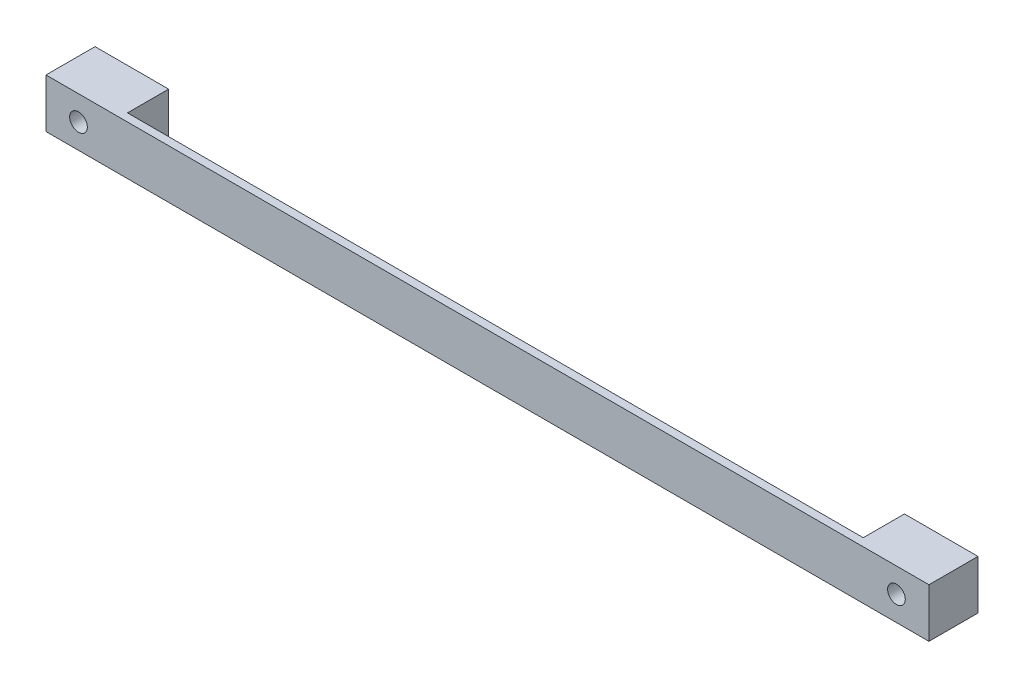
SolidWorks part; units mm, degrees
ref_plane "Front Plane" through (0, 0, 0) normal (0, 0, 1) x (1, 0, 0)
ref_plane "Top Plane" through (0, 0, 0) normal (0, 1, 0) x (1, 0, 0)
ref_plane "Right Plane" through (0, 0, 0) normal (1, 0, 0) x (0, 0, -1)
sketch "Sketch1" plane through (0, 0, 0) normal (0, 0, 1) x (1, 0, 0)
  line L1 (0, 0) -> (228.6, 0)
  line L2 (0, 0) -> (0, 12.7)
  line L3 (0, 12.7) -> (228.6, 12.7)
  line L4 (228.6, 0) -> (228.6, 12.7)
  dimension "D1" = 12.7
  dimension "D2" = 228.6
extrude "Boss-Extrude1" add sketch "Sketch1" along normal blind 12.7
ref_plane "Plane2" through (114.3, 0, 0) normal (1, 0, 0) x (0, 0, -1)
sketch "Sketch2" plane through (114.3, 0, 0) normal (1, 0, 0) x (0, 0, -1)
  line L0 (-10.6566, 12.7) -> (0, 0)
  line L1 (-12.7, 12.7) -> (0, 12.7) construction
  line L2 (0, 0) -> (0, 12.7) construction
  line L3 (0, 0) -> (0, 12.7)
  line L4 (0, 12.7) -> (-10.6566, 12.7)
  point P6 (0, 2.3854)
  point P8 (0, 0)
  point P10 (0, 0)
  dimension "D1" = 50
extrude "Cut-Extrude1" cut sketch "Sketch2" against normal mid plane 190.5
sketch "Sketch4" plane through (0, 0, 0) normal (0, 0, -1) x (-1, 0, 0)
  line L0 (-5.2387, 6.35) -> (-5.2387, 8.4174) construction
  line L1 (-11.5887, 9.525) -> (-5.2387, 9.525)
  line L2 (-11.5887, 9.525) -> (-11.5887, 3.175)
  line L3 (-11.5887, 3.175) -> (-5.2387, 3.175)
  line L4 (-5.2387, 9.525) -> (-5.2387, 3.175)
  line L5 (-11.5887, 9.525) -> (-5.2387, 3.175) construction
  line L6 (-11.5887, 3.175) -> (-5.2387, 9.525) construction
  line L7 (-6.3463, 9.525) -> (-10.4812, 9.525) construction
  point P0 (-8.4137, 6.35)
extrude "Cut-Extrude2" cut sketch "Sketch4" against normal blind 6.35
sketch "Sketch5" plane through (0, 0, 6.35) normal (0, 0, -1) x (-1, 0, 0)
  line L0 (-8.4137, 6.35) -> (-11.5887, 6.35) construction
  line L1 (-11.5887, 9.525) -> (-11.5887, 3.175) construction
  line L2 (-8.4137, 9.525) -> (-8.4137, 6.35) construction
  line L3 (-5.2387, 9.525) -> (-11.5887, 9.525) construction
  line L4 (-11.5887, 9.525) -> (-11.5887, 3.175) construction
  circle A0 centre (-8.4137, 6.35) radius 2.286
  dimension "D1" = 4.572
extrude "Cut-Extrude3" cut sketch "Sketch5" against normal through all
mirror "Mirror1" about plane through (114.3, 0, 0) normal (1, 0, 0) of "Cut-Extrude2", "Cut-Extrude3"
